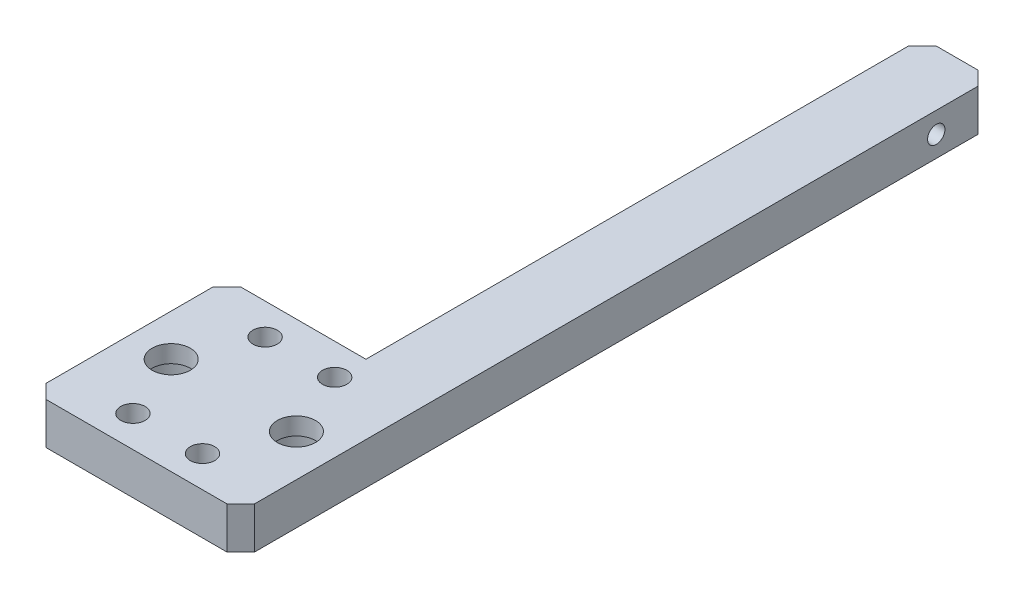
SolidWorks part; units mm, degrees
ref_plane "前视基准面" through (0, 0, 0) normal (0, 0, 1) x (1, 0, 0)
ref_plane "上视基准面" through (0, 0, 0) normal (0, 1, 0) x (1, 0, 0)
ref_plane "右视基准面" through (0, 0, 0) normal (1, 0, 0) x (0, 0, -1)
sketch "草图1" plane through (0, 0, 0) normal (0, 1, 0) x (1, 0, 0)
  line L1 (-15, 14) -> (15, 14)
  line L2 (-15, 14) -> (-15, -14)
  line L3 (-15, -14) -> (15, -14)
  line L4 (15, 14) -> (15, -14)
  line L5 (-15, 14) -> (15, -14) construction
  line L6 (-15, -14) -> (15, 14) construction
  point P0 (0, 0)
  dimension "D1" = 28
  dimension "D2" = 30
extrude "凸台-拉伸1" add sketch "草图1" along normal blind 6
sketch "草图2" plane through (0, 6, 0) normal (0, 1, 0) x (1, 0, 0)
  line L0 (-15, 0) -> (15, 0) construction
  line L1 (-15, 14) -> (-15, -14) construction
  line L2 (15, -14) -> (15, 14) construction
  line L3 (0, 14) -> (0, -14) construction
  line L4 (15, 14) -> (-15, 14) construction
  line L5 (-15, -14) -> (15, -14) construction
  circle A0 centre (-5, 9.5) radius 1.75
  circle A1 centre (5, 9.5) radius 1.75
  circle A2 centre (-5, -9.5) radius 1.75
  circle A3 centre (5, -9.5) radius 1.75
  dimension "D3" = 3.5
  dimension "D1" = 10
  dimension "D2" = 19
extrude "切除-拉伸1" cut sketch "草图2" against normal through all
sketch "草图4" plane through (0, 0, 0) normal (0, -1, 0) x (1, 0, 0)
  line L0 (-15, 0) -> (15, 0) construction
  line L1 (-15, -14) -> (-15, 14) construction
  line L2 (15, 14) -> (15, -14) construction
  line L3 (0, 14) -> (0, -14) construction
  line L4 (-15, 14) -> (15, 14) construction
  line L5 (15, -14) -> (-15, -14) construction
  circle A0 centre (-9, 0) radius 2.75
  circle A1 centre (9, 0) radius 2.75
  dimension "D3" = 5.5
  dimension "D2" = 18
extrude "切除-拉伸4" cut sketch "草图4" against normal through all and the other way blind 3.5
sketch "草图6" plane through (0, 0, 0) normal (0, -1, 0) x (1, 0, 0)
  circle A0 centre (-9, 0) radius 5
  circle A1 centre (9, 0) radius 5
  dimension "D1" = 10
  dimension "D2" = 10
sketch "草图7" plane through (0, 6, 0) normal (0, 1, 0) x (1, 0, 0)
  line L9 (15, 74) -> (15, 14)
  line L12 (15, 74) -> (15, 94)
  line L13 (15, 94) -> (5, 94)
  line L14 (5, 94) -> (5, 64)
  line L16 (5, 64) -> (5, 14)
  line L17 (15, 14) -> (5, 14)
extrude "凸台-拉伸2" add sketch "草图7" against normal blind 6 contours L14 L16 L17 L9 L12 L13
extrude "切除-拉伸5" cut sketch "草图6" against normal blind 3.5
chamfer "倒角1" distance 2 angle 45 5 edges at (15, 3, 14) (-15, 3, 14) (5, 3, -94) (15, 3, -94) (-15, 3, -14)
sketch "草图8" plane through (5, 0, 0) normal (-1, 0, 0) x (0, 0, 1)
  line L0 (-92, 6) -> (-14, 6) construction
  line L1 (-94, 0) -> (-94, 6) construction
  circle A1 centre (-86, 3) radius 1.25
  point P0 (-86, 3)
  dimension "D1" = 3
  dimension "D2" = 8
extrude "切除-拉伸6" cut sketch "草图8" against normal up to next
